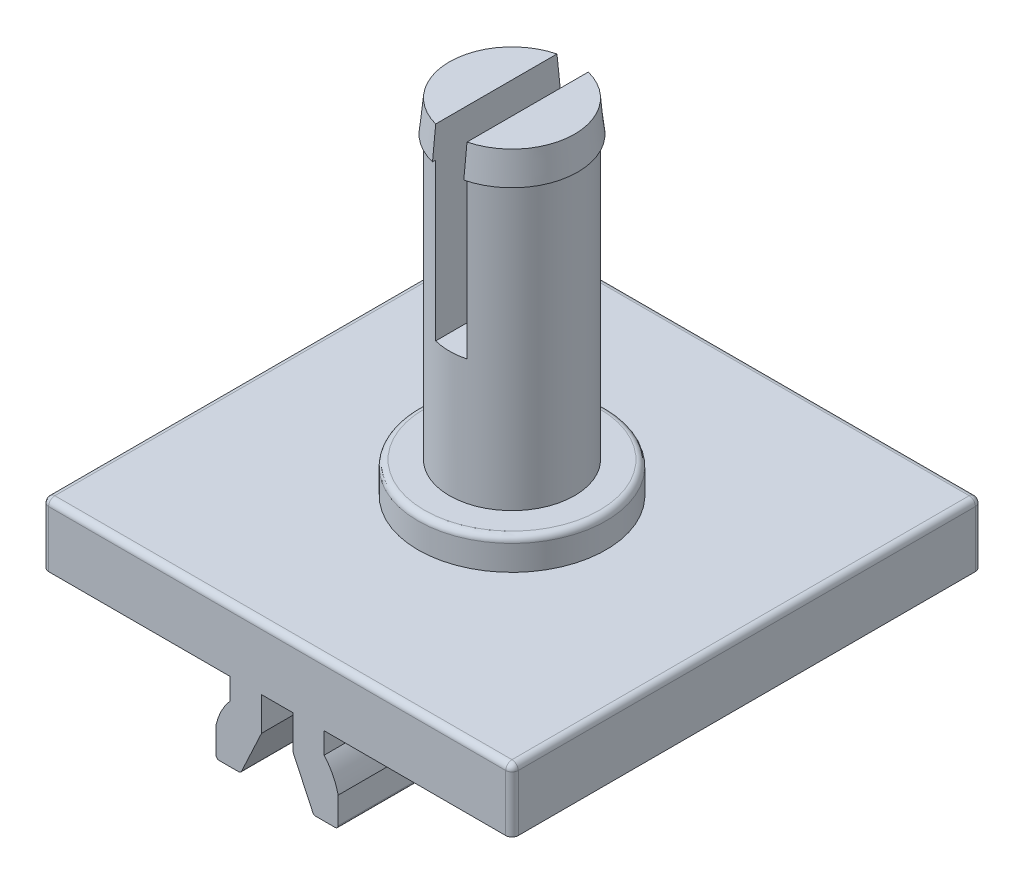
SolidWorks part; units mm, degrees
ref_plane "前视基准面" through (0, 0, 0) normal (0, 0, 1) x (1, 0, 0)
ref_plane "上视基准面" through (0, 0, 0) normal (0, 1, 0) x (1, 0, 0)
ref_plane "右视基准面" through (0, 0, 0) normal (1, 0, 0) x (0, 0, -1)
sketch "草图1" plane through (0, 0, 0) normal (0, 1, 0) x (1, 0, 0)
  line L0 (7.5, 7.5) -> (7.5, -7.5)
  line L1 (7.5, 7.5) -> (-7.5, 7.5)
  line L2 (7.5, -7.5) -> (-7.5, -7.5)
  line L3 (-7.5, 7.5) -> (-7.5, -7.5)
  line L4 (7.5, 7.5) -> (-7.5, -7.5) construction
  line L5 (7.5, -7.5) -> (-7.5, 7.5) construction
  point P1 (0, 0)
  dimension "D1" = 15
  dimension "D2" = 15
extrude "凸台-拉伸1" add sketch "草图1" along normal blind 2
sketch "草图2" plane through (0, 2, 0) normal (0, 1, 0) x (1, 0, 0)
  circle A0 centre (0, 0) radius 3
  dimension "D1" = 6
extrude "凸台-拉伸2" add sketch "草图2" along normal blind 1
sketch "草图3" plane through (0, 3, 0) normal (0, 1, 0) x (1, 0, 0)
  circle A0 centre (0, 0) radius 2
  dimension "D1" = 4
extrude "凸台-拉伸3" add sketch "草图3" along normal blind 10
sketch "草图4" plane through (0, 0, 0) normal (0, 0, 1) x (1, 0, 0)
  line L0 (0, 13) -> (-2, 13)
  line L1 (2, 13) -> (-2, 13) construction
  line L2 (-2, 13) -> (-2.1, 12)
  line L3 (-2.1, 12) -> (0, 12)
  line L4 (0, 12) -> (0, 13)
  dimension "D1" = 1
  dimension "D2" = 2.1
revolve "旋转1" add sketch "草图4" angle 360 about L4
sketch "草图5" plane through (0, 13, 0) normal (0, 1, 0) x (1, 0, 0)
  line L0 (0.5, 3) -> (-0.5, 3)
  line L1 (0.5, 3) -> (0.5, -3)
  line L2 (-0.5, 3) -> (-0.5, -3)
  line L3 (0.5, -3) -> (-0.5, -3)
  line L4 (0.5, 3) -> (-0.5, -3) construction
  line L5 (-0.5, 3) -> (0.5, -3) construction
  point P1 (0, 0)
  dimension "D1" = 6
  dimension "D2" = 1
extrude "切除-拉伸1" cut sketch "草图5" against normal blind 6
sketch "草图6" plane through (0, 0, 0) normal (0, 0, 1) x (1, 0, 0)
  line L0 (0, 0) -> (0, -2) construction
  line L1 (0, -2) -> (0, -2.5) construction
  line L2 (-0.5, 0) -> (-1.5, 0)
  line L3 (-1.5, 0) -> (-1.5, -0.6771)
  line L4 (-1.1658, -2.5) -> (-1.95, -2.5)
  line L5 (-1.95, -2.5) -> (-1.95, -1.5556)
  line L6 (0.5, 0) -> (0.5, -1.0723)
  line L7 (-0.5, 0) -> (-0.5, -1.0723)
  line L8 (-0.5, -1.0723) -> (-1.1658, -2.5)
  line L9 (0.5, -1.0723) -> (1.1658, -2.5)
  line L10 (1.1658, -2.5) -> (1.95, -2.5)
  line L11 (1.95, -2.5) -> (1.95, -1.5556)
  line L12 (1.5, 0) -> (1.5, -0.6771)
  line L13 (0.5, 0) -> (1.5, 0)
  arc A0 (-1.5, -0.6771) -> (-1.95, -1.5556) centre (0, -2) ccw
  arc A1 (1.5, -0.6771) -> (1.95, -1.5556) centre (0, -2) cw
  dimension "D1" = 2
  dimension "D2" = 0.5
  dimension "D3" = 1.5
  dimension "D4" = 1.95
  dimension "D5" = 0.5
  dimension "D6" = 65
extrude "凸台-拉伸4" add sketch "草图6" along normal blind 7.5 and the other way blind 7.5
fillet "圆角1" radius 0.2 9 edges at (-7.5, 1, -7.5) (7.5, 1, -7.5) (7.5, 1, 7.5) (-7.5, 1, 7.5) (7.5, 2, 0) (0, 2, -7.5) (-7.5, 2, 0) (0, 2, 7.5) (0, 3, 3)
fillet "圆角2" radius 0.1 4 edges at (-1.95, -2.5, 0) (-1.1658, -2.5, 0) (1.1658, -2.5, 0) (1.95, -2.5, 0)
